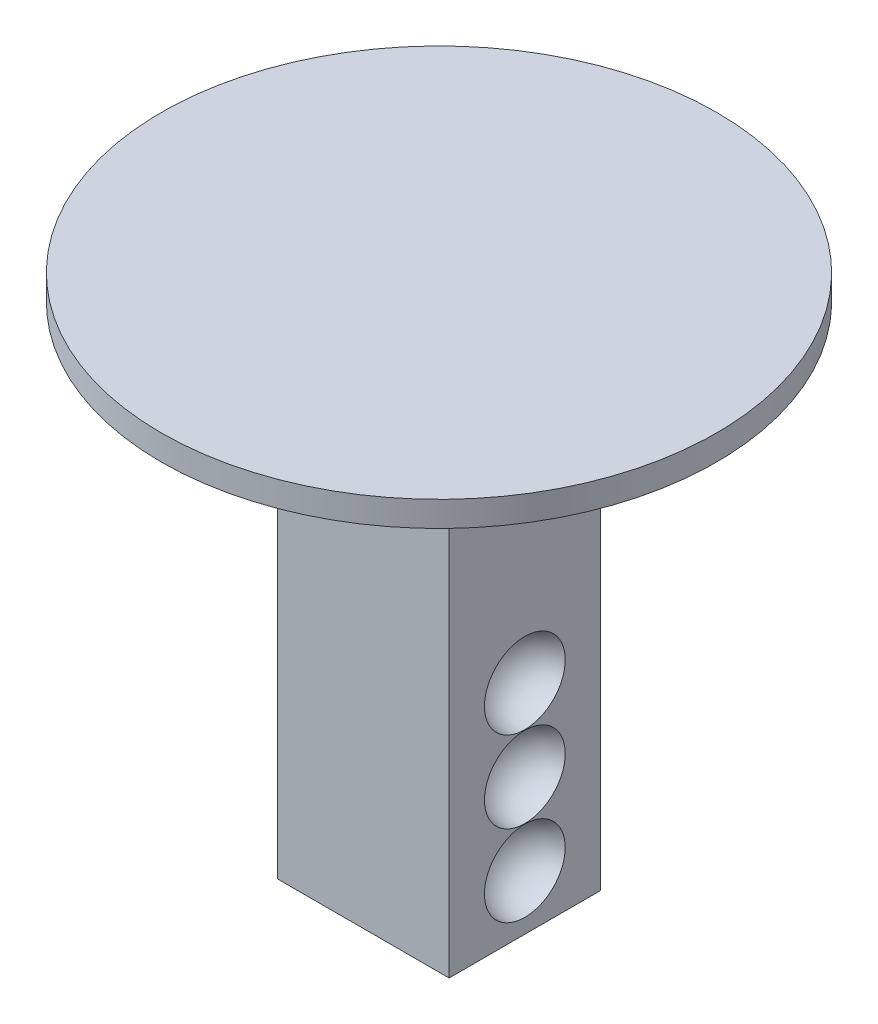
SolidWorks part; units mm, degrees
ref_plane "前视基准面" through (0, 0, 0) normal (0, 0, 1) x (1, 0, 0)
ref_plane "上视基准面" through (0, 0, 0) normal (0, 1, 0) x (1, 0, 0)
ref_plane "右视基准面" through (0, 0, 0) normal (1, 0, 0) x (0, 0, -1)
other "Configuration Table"
sketch "草图5" plane through (0, 0, 0) normal (0, 0, 1) x (1, 0, 0)
  line L1 (-17, 70) -> (0, 70)
  line L2 (-17, 70) -> (-17, -30)
  line L3 (-17, -30) -> (0, -30)
  line L4 (0, 70) -> (0, -30)
  dimension "D1" = 100
  dimension "D2" = 30
  dimension "D3" = 17
extrude "凸台-拉伸1" add sketch "草图5" along normal blind 15 and the other way blind 15
sketch "草图7" plane through (0, 0, 0) normal (0, 0, 1) x (1, 0, 0)
  line L2 (-17, 70) -> (-17, -30) construction
  line L3 (-17, -30) -> (0, -30) construction
  line L4 (-17, 5) -> (-17, -11)
  arc A1 (-17, -11) -> (-17, 5) centre (-17, -3) ccw
  dimension "D1" = 27
  dimension "D2" = 8
revolve "切除-旋转1" cut sketch "草图7" angle 360 about L4
pattern_linear "阵列(线性)1" count 2 spacing 16.1 along (0, 1, 0) count 2 spacing 16.1 along (0, -1, 0) of "切除-旋转1" pattern seed only yes
mirror "镜向2" about plane through (0, 0, 0) normal (1, 0, 0) of "凸台-拉伸1"
mirror "镜向3" about plane through (0, 0, 0) normal (1, 0, 0) of "切除-旋转1"
mirror "镜向4" about plane through (0, 0, 0) normal (1, 0, 0) of "阵列(线性)1"
sketch "草图8" plane through (0, 0, 0) normal (0, 0, 1) x (1, 0, 0)
  line L0 (-17, -30) -> (17, -30) construction
  line L1 (-8, -8) -> (0, -8)
  line L2 (-8, -8) -> (-8, -30)
  line L3 (-8, -30) -> (0, -30)
  line L4 (0, -8) -> (0, -30)
  dimension "D1" = 8
  dimension "D2" = 22
revolve "切除-旋转2" cut sketch "草图8" angle 360 about L4
sketch "草图9" plane through (0, 0, 0) normal (0, 0, 1) x (1, 0, 0)
  line L0 (17, 70) -> (-17, 70) construction
  line L1 (0, 70) -> (55, 70)
  line L2 (0, 70) -> (0, 75)
  line L3 (0, 75) -> (55, 75)
  line L4 (55, 70) -> (55, 75)
  dimension "D1" = 55
  dimension "D2" = 5
revolve "旋转1" add sketch "草图9" angle 360 about L2
